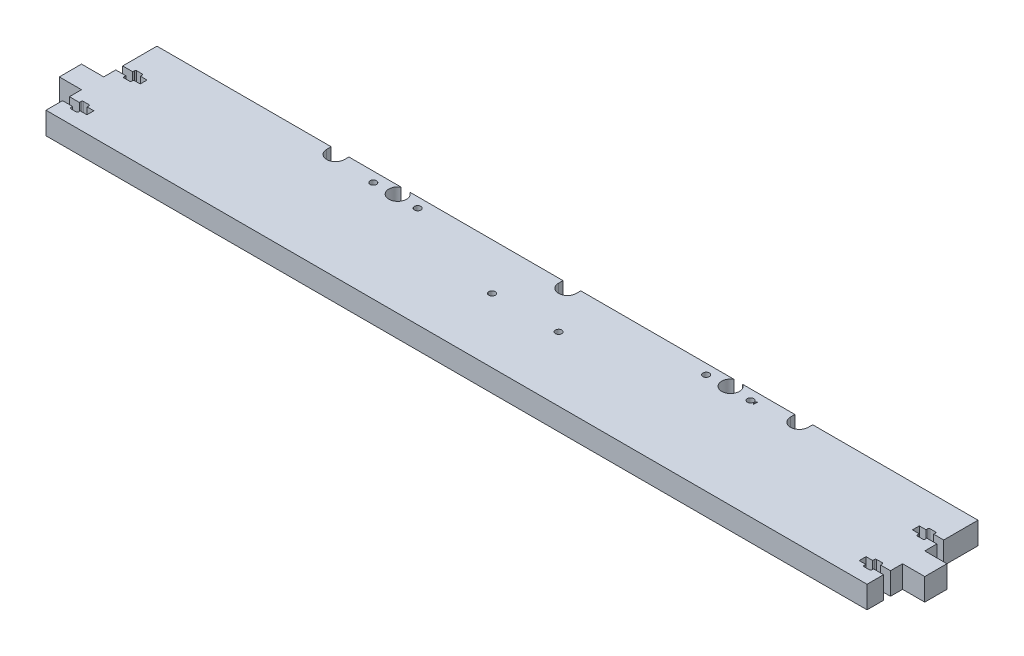
SolidWorks part; units mm, degrees
ref_plane "Front Plane" through (0, 0, 0) normal (0, 0, 1) x (1, 0, 0)
ref_plane "Top Plane" through (0, 0, 0) normal (0, 1, 0) x (1, 0, 0)
ref_plane "Right Plane" through (0, 0, 0) normal (1, 0, 0) x (0, 0, -1)
sketch "Sketch1" plane through (0, 0, 0) normal (0, 1, 0) x (1, 0, 0)
  line L0 (0, 25) -> (0, -25)
  line L1 (-185, 25) -> (0, 25)
  line L2 (-185, 25) -> (-185, -25) construction
  line L3 (-185, -25) -> (0, -25)
  line L4 (-185, -4) -> (-195, -4) construction
  line L5 (-185, 25) -> (0, 0) construction
  line L6 (-185, -25) -> (0, 0) construction
  line L7 (-185, -9) -> (-195, -9)
  line L8 (-195, -9) -> (-195, 1)
  line L9 (-195, 1) -> (-185, 1)
  line L10 (-185, 1) -> (-185, 25)
  line L11 (-185, -9) -> (-185, -25)
  line L47 (0, -25) -> (0, 25) construction
  line L89 (0, -25) -> (0, 25) construction
  point P0 (0, 0)
  dimension "D1" = 185
  dimension "D25" = 25
  dimension "D4" = 50
  dimension "D3" = 21
  dimension "D5" = 10
  dimension "D6" = 10
  dimension "D7" = 5
extrude "MainBody" add sketch "Sketch1" along normal blind 10 contours L3 region at (-93.5428, 0, 0.0428)
sketch "Sketch5" plane through (0, 10, 0) normal (0, 1, 0) x (1, 0, 0)
  line L0 (-185, 8) -> (-174, 8) construction
  line L1 (-185, 1) -> (-185, 25) construction
  line L2 (-185, 9.55) -> (-174, 9.55) construction
  line L3 (-174, 9.55) -> (-174, 6.45) construction
  line L4 (-174, 6.45) -> (-185, 6.45) construction
  line L5 (-185, 9.55) -> (-180.5, 9.55)
  line L6 (-180.5, 9.55) -> (-180.5, 10.35)
  line L7 (-180, 10.85) -> (-177.5, 10.85)
  line L8 (-177, 10.35) -> (-177, 9.55)
  line L9 (-177, 9.55) -> (-174, 9.55)
  line L10 (-174, 9.55) -> (-174, 6.45)
  line L11 (-185, 6.45) -> (-185, 9.55)
  line L12 (-195, -9) -> (-195, 1) construction
  line L13 (-185, 6.45) -> (-174, 6.45) construction
  line L14 (-177, 6.45) -> (-174, 6.45)
  line L15 (-177, 5.65) -> (-177, 6.45)
  line L16 (-180, 5.15) -> (-177.5, 5.15)
  line L17 (-180.5, 6.45) -> (-180.5, 5.65)
  line L18 (-185, 6.45) -> (-180.5, 6.45)
  line L19 (-185, 1) -> (-185, -9) construction
  line L20 (-195, -4) -> (-185, -4) construction
  line L21 (-195, -9) -> (-195, 1) construction
  line L22 (-185, -14.45) -> (-174, -14.45) construction
  line L23 (-174, -14.45) -> (-185, -14.45) construction
  line L24 (-174, -17.55) -> (-174, -14.45) construction
  line L25 (-185, -17.55) -> (-174, -17.55) construction
  line L26 (-185, -16) -> (-174, -16) construction
  line L27 (-185, -14.45) -> (-180.5, -14.45)
  line L28 (-180.5, -14.45) -> (-180.5, -13.65)
  line L29 (-180, -13.15) -> (-177.5, -13.15)
  line L30 (-177, -13.65) -> (-177, -14.45)
  line L31 (-177, -14.45) -> (-174, -14.45)
  line L32 (-185, -14.45) -> (-185, -17.55)
  line L33 (-174, -17.55) -> (-174, -14.45)
  line L34 (-177, -17.55) -> (-174, -17.55)
  line L35 (-177, -18.35) -> (-177, -17.55)
  line L36 (-180, -18.85) -> (-177.5, -18.85)
  line L37 (-180.5, -17.55) -> (-180.5, -18.35)
  line L38 (-185, -17.55) -> (-180.5, -17.55)
  line L39 (-185, 6.45) -> (-174, 6.45) construction
  arc A0 (-177.5, 10.85) -> (-177, 10.35) centre (-177.5, 10.35) cw
  arc A1 (-180.5, 10.35) -> (-180, 10.85) centre (-180, 10.35) cw
  arc A2 (-180.5, 5.65) -> (-180, 5.15) centre (-180, 5.65) ccw
  arc A3 (-177.5, 5.15) -> (-177, 5.65) centre (-177.5, 5.65) ccw
  arc A4 (-177.5, -13.15) -> (-177, -13.65) centre (-177.5, -13.65) cw
  arc A5 (-180.5, -13.65) -> (-180, -13.15) centre (-180, -13.65) cw
  arc A6 (-180.5, -18.35) -> (-180, -18.85) centre (-180, -18.35) ccw
  arc A7 (-177.5, -18.85) -> (-177, -18.35) centre (-177.5, -18.35) ccw
  point P6 (-195, -4)
  point P17 (-177, 10.85)
  point P20 (-180.5, 10.85)
  point P29 (-180.5, 5.15)
  point P30 (-177, 5.15)
  point P61 (-177, -13.15)
  point P62 (-180.5, -13.15)
  point P63 (-180.5, -18.85)
  point P64 (-177, -18.85)
  dimension "D8" = 0.5
  dimension "D1" = 11
  dimension "D2" = 1.55
  dimension "D4" = 3.5
  dimension "D5" = 8
  dimension "D6" = 2.85
  dimension "D7" = 12
extrude "ScrewCutouts" cut sketch "Sketch5" against normal through all
mirror "Mirror1" about plane through (0, 0, 0) normal (1, 0, 0) of "ScrewCutouts", "MainBody"
sketch "Sketch3" plane through (0, 10, 0) normal (0, 1, 0) x (1, 0, 0)
  line L0 (2, 25) -> (2, -25) construction
  line L1 (-185, 25) -> (185, 25) construction
  line L2 (-185, -25) -> (185, -25) construction
  line L3 (-63, 20.5) -> (-83, 20.5) construction
  line L4 (-73, 17.5) -> (-73, 25.5) construction
  line L5 (77, 17.5) -> (77, 25.5) construction
  line L6 (67, 20.5) -> (87, 20.5) construction
  circle A0 centre (-73, 21.5) radius 4
  circle A1 centre (-83, 20.5) radius 1.45
  circle A2 centre (-63, 20.5) radius 1.45
  circle A3 centre (67, 20.5) radius 1.45
  circle A4 centre (87, 20.5) radius 1.45
  circle A5 centre (77, 21.5) radius 4
  dimension "D2" = 8
  dimension "D4" = 2.9
  dimension "D1" = 3.5
  dimension "D5" = 75
  dimension "D6" = 2
  dimension "D3" = 10
  dimension "D7" = 1
extrude "RodCutouts" cut sketch "Sketch3" against normal through all
sketch "Sketch6" plane through (0, 10, 0) normal (0, 1, 0) x (1, 0, 0)
  line L0 (-73, 21.5) -> (77, 21.5) construction
  line L1 (2, 21.5) -> (2, -25) construction
  line L2 (-185, -25) -> (185, -25) construction
  line L3 (17, 4) -> (-13, 4) construction
  line L4 (-71.0635, 25) -> (75.0635, 25) construction
  circle A0 centre (-13, 4) radius 1.45
  circle A1 centre (17, 4) radius 1.45
  point P13 (2, 4)
  dimension "D3" = 21
  dimension "D1" = 2.9
  dimension "D2" = 15
extrude "Cut-Extrude1" cut sketch "Sketch6" against normal through all
sketch "Sketch7" plane through (0, 10, 0) normal (0, 1, 0) x (1, 0, 0)
  line L0 (-73, 21.5) -> (77, 21.5) construction
  line L1 (2, 21.5) -> (2, -25) construction
  line L3 (-102.5, 25) -> (-102.5, 23) construction
  line L4 (-185, 25) -> (-74.9365, 25) construction
  line L5 (-98.5, 25) -> (-98.5, 23)
  line L6 (-106.5, 25) -> (-106.5, 23)
  line L7 (106.5, 25) -> (106.5, 23) construction
  line L8 (102.5, 25) -> (102.5, 23)
  line L9 (110.5, 25) -> (110.5, 23)
  line L12 (-185, -25) -> (185, -25) construction
  arc A0 (-98.5, 25) -> (-106.5, 25) centre (-102.5, 25) ccw
  arc A1 (-106.5, 23) -> (-98.5, 23) centre (-102.5, 23) ccw
  arc A2 (102.5, 25) -> (110.5, 25) centre (106.5, 25) cw
  arc A3 (110.5, 23) -> (102.5, 23) centre (106.5, 23) cw
  point P12 (-102.5, 24)
  point P19 (106.5, 24)
  dimension "D1" = 4
  dimension "D2" = 2
  dimension "D3" = 104.5
extrude "BedAdjustmentScrewCutout" cut sketch "Sketch7" against normal through all
sketch "Sketch8" plane through (0, 10, 0) normal (0, 1, 0) x (1, 0, 0)
  line L0 (88.25, 20.5) -> (89.25, 20.5) construction
  line L1 (88.45, 20.5) -> (88.45, 25) construction
  line L2 (88.25, 20.5) -> (89.25, 21.5)
  line L3 (89.25, 21.5) -> (89.25, 19.5)
  line L4 (88.25, 20.5) -> (89.25, 19.5)
  line L5 (78.9365, 25) -> (102.5, 25) construction
  circle A1 centre (87, 20.5) radius 1.45 construction
  point P9 (89.25, 20.5)
  dimension "D1" = 1
  dimension "D2" = 1
  dimension "D3" = 0.2
extrude "DirectionKey" cut sketch "Sketch8" against normal through all
sketch "Sketch9" plane through (0, 10, 0) normal (0, 1, 0) x (1, 0, 0)
  line L0 (-13, 4) -> (17, 4) construction
  line L1 (2, 4) -> (2, 25) construction
  line L2 (-71.0635, 25) -> (75.0635, 25) construction
  line L3 (2, 27) -> (2, 23) construction
  line L4 (6, 27) -> (6, 23)
  line L5 (-2, 27) -> (-2, 23)
  arc A0 (6, 27) -> (-2, 27) centre (2, 27) ccw
  arc A1 (-2, 23) -> (6, 23) centre (2, 23) ccw
  point P10 (2, 25)
  dimension "D1" = 4
  dimension "D2" = 2
extrude "Cut-Extrude2" cut sketch "Sketch9" against normal through all
equation "\"Y-ROD-SPACING\"=75"
equation "\"Y-BED-OFFSET\"=2"
equation "\"T-SLOT-NUT-FILLET-RADIUS\"=0.5"
equation "\"T-SLOT-SCREW-SHAFT-RADIUS\"=1.55"
equation "\"T-SLOT-SCREW-SHAFT-CUTOUT-LENGTH\"=11"
equation "\"T-SLOT-NUT-DEPTH\"=3.5"
equation "\"T-SLOT-NUT-WIDTH\"=2.85"
equation "\"T-SLOT-NUT-END-DISTANCE\"=8"
equation "\"ACRYLIC-TAB-CUTOUT-SIZE\"=\"ACRYLIC-THICKNESS\"+\"ACRYLIC-TAB-TOLERANCE\"*2"
equation "\"ACRYLIC-M3-HOLE\"=2.9"
equation "\"D1@Sketch5\"=\"T-SLOT-SCREW-SHAFT-CUTOUT-LENGTH\""
equation "\"D2@Sketch5\"=\"T-SLOT-SCREW-SHAFT-RADIUS\""
equation "\"D4@Sketch5\"=\"T-SLOT-NUT-DEPTH\""
equation "\"D5@Sketch5\"=\"T-SLOT-NUT-END-DISTANCE\""
equation "\"D6@Sketch5\"=\"T-SLOT-NUT-WIDTH\""
equation "\"D8@Sketch5\"=\"T-SLOT-NUT-FILLET-RADIUS\""
equation "\"D4@Sketch3\"=\"ACRYLIC-M3-HOLE\""
equation "\"D5@Sketch3\"=\"Y-ROD-SPACING\""
equation "\"D6@Sketch3\"=\"Y-BED-OFFSET\""
equation "\"Y-BED-ROD-INSET\"=3.5"
equation "\"D1@Sketch3\"=\"Y-BED-ROD-INSET\""
equation "\"SMOOTHROD-CAP-SCREW-DISTANCE\"=20"
equation "\"D3@Sketch3\"=\"SMOOTHROD-CAP-SCREW-DISTANCE\"/2"
equation "\"ACRYLIC-TAB-WIDTH\"=\"ACRYLIC-THICKNESS\""
equation "\"FRAME-WIDTH-INNER\"=370"
equation "\"D6@Sketch1\"=\"ACRYLIC-TAB-WIDTH\""
equation "\"D5@Sketch1\"=\"ACRYLIC-TAB-WIDTH\""
equation "\"D1@Sketch1\"=\"FRAME-WIDTH-INNER\"/2"
equation "\"X-ROD-SPACING\"=45"
equation "\"Z-ROD-SPACING\"=17.5"
equation "\"ACRYLIC-THICKNESS\"=10"
equation "\"ACRYLIC-THICKNESS2\"=4.5"
equation "\"NEMA17-HOLE-SPACING\"=31"
equation "\"NEMA17-CENTRAL-CUTOUT\"=22.5"
equation "\"Z-BRACKET-REACH\"=57"
equation "\"TOP-BRACKET-SPACING\"=40"
equation "\"SMOOTHROD-X-LENGTH\"=350"
equation "\"SMOOTHROD-Y-LENGTH\"=350"
equation "\"SMOOTHROD-Z-LENGTH\"=350"
equation "\"SMOOTHROD-TIGHTENING-HEADROOM\"=.25"
equation "\"LEADSCREW-Z-LENGTH\"=300"
equation "\"SCREW-LENGTH-FRAME\"=\"ACRYLIC-THICKNESS\" + 10"
equation "\"SCREW-HEAD-RADIUS\"=6"
equation "\"PRINTED-X-SMOOTHROD-DIAMETER\"=8.8"
equation "\"PRINTED-X-SMOOTHROD-CUTOUT\"=10"
equation "\"PRINTED-X-BASE-HEIGHT\"=10"
equation "\"PRINTED-LM8UU-CUTOUT-SIZE\"=15.5"
equation "\"PRINTED-LM8UU-CUTOUT-LENGTH\"=24.5"
equation "\"PRINTED-X-IDLER-HEIGHT\"=16"
equation "\"PSU-MOUNTING-WIDTH\"=95"
equation "\"PSU-MOUNTING-HEIGHT\"=177"
equation "\"D1@MainBody\"=\"ACRYLIC-THICKNESS\""
equation "\"D7@Sketch1\"=\"ACRYLIC-TAB-WIDTH\"/2"
equation "\"D1@Sketch6\"=\"ACRYLIC-M3-HOLE\""
equation "\"Y-BELT-TO-ROD-DISTANCE\"=20"
equation "\"Y-BED-SCREW-SPACING\"=209"
equation "\"Z-ROD-INSET\"=13.5"
equation "\"SPOOL-HOLDER-ROD-SPACING\"=150"
equation "\"D3@Sketch7\"=\"Y-BED-SCREW-SPACING\"/2"
equation "\"Y-BED-SCREW-CUTOUT-SLOT-HEIGHT\"=2"
equation "\"D2@Sketch7\"=\"Y-BED-SCREW-CUTOUT-SLOT-HEIGHT\""
equation "\"ACRYLIC-TAB-TOLERANCE\"=-.05"
equation "\"SCREW-LENGTH-MOTOR\"=\"ACRYLIC-THICKNESS\" + 5"
equation "\"SCREW-LENGTH-EXTRUDER\"=28"
equation "\"PRINTED-M3-HOLE\"=3.5"
equation "\"ACRYLIC-X-CARRIAGE-WIDTH\"=55"
equation "\"ACRYLIC-X-CARRIAGE-HEIGHT\"=75"
equation "\"ACRYLIC-X-CARRIAGE-LM8UU-CUTOUT-WIDTH\"=24.25"
equation "\"ACRYLIC-X-CARRIAGE-LM8UU-CUTOUT-HEIGHT\"=11.0"
equation "\"ACRYLIC-X-CARRIAGE-SCREW-SPACING-X\"=15"
equation "\"ACRYLIC-X-CARRIAGE-SCREW-SPACING-Y\"=33"
equation "\"ACRYLIC-X-CARRIAGE-CENTER-TAB-SPACING\"=14"
equation "\"ACRYLIC-X-CARRIAGE-EXTRUDER-OFFSET\"=26"
equation "\"ACRYLIC-X-CARRIAGE-EXTRUDER-ANGLE\"=90"
equation "\"ACRYLIC-X-CARRIAGE-EXTRUDER-SHELF-DEPTH\"=\"ACRYLIC-X-CARRIAGE-EXTRUDER-OFFSET\" + 28"
equation "\"ACRYLIC-X-CARRIAGE-EXTRUDER-BRACE-SPACING\"=23"
equation "\"ACRYLIC-X-CARRIAGE-EXTRUDER-BRACE-TAB-OFFSET\"=20"
equation "\"ACRYLIC-X-CARRIAGE-EXTRUDER-BRACE-HEIGHT\"=35"
equation "\"ACRYLIC-X-CARRIAGE-EXTRUDER-BRACE-SCREW-SPACING\"=22"
equation "\"ACRYLIC-X-CARRIAGE-DUAL-WIDTH-MULTIPLIER\"=1.65"
equation "\"ACRYLIC-X-CARRIAGE-DUAL-HOTEND-SPACING\"=42"
equation "\"ACRYLIC-X-CARRIAGE-DUAL-WIDTH\"=75"
equation "\"ACRYLIC-X-CARRIAGE-DUAL-HOTEND-SEPARATION\"=36"
equation "\"ACRYLIC-X-CARRIAGE-DUAL-MOUNT-PLATE-DEPTH\"=75"
equation "\"ACRYLIC-X-CARRIAGE-DUAL-MOUNT-BRACE-WIDTH\"=33"
equation "\"ACRYLIC-X-CARRIAGE-DUAL-MOUNT-SCREW-WIDTH\"=40"
equation "\"BLOWER-FAN-WIDTH\"=15"
equation "\"D2@Sketch9\"=\"Y-BED-SCREW-CUTOUT-SLOT-HEIGHT\""
